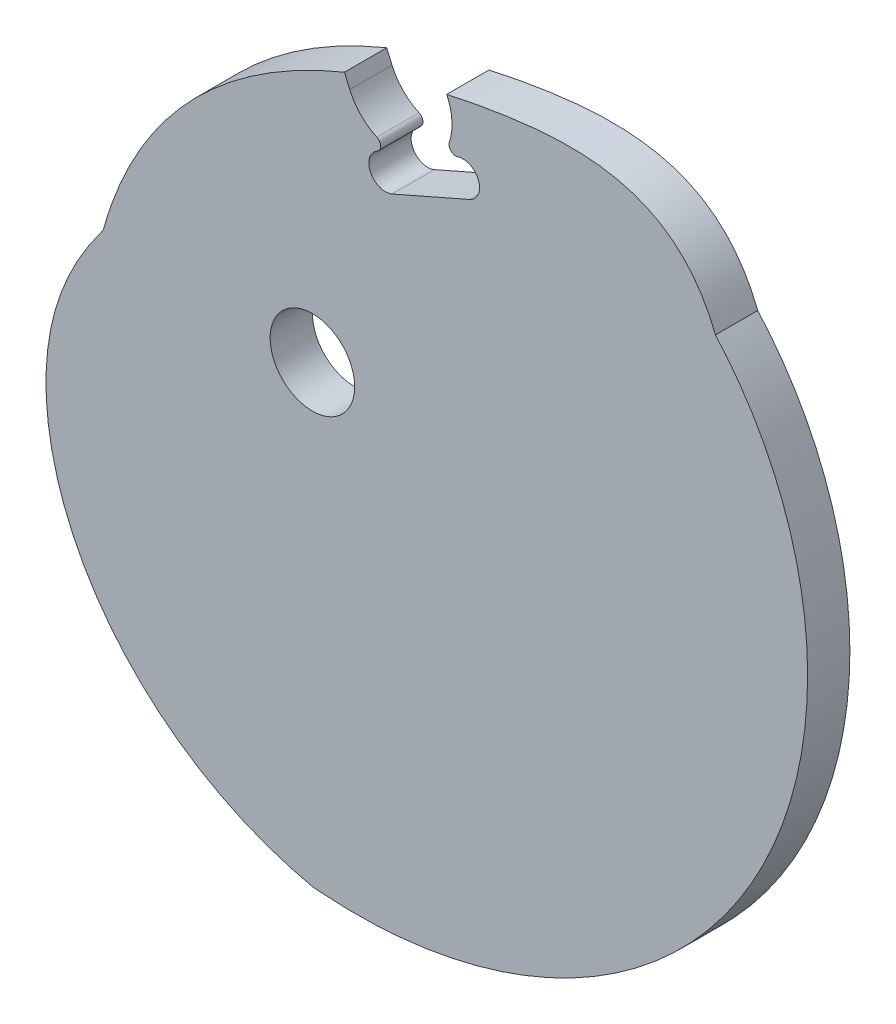
SolidWorks part; units mm, degrees
ref_plane "Front Plane" through (0, 0, 0) normal (0, 0, 1) x (1, 0, 0)
ref_plane "Top Plane" through (0, 0, 0) normal (0, 1, 0) x (1, 0, 0)
ref_plane "Right Plane" through (0, 0, 0) normal (1, 0, 0) x (0, 0, -1)
curve "Curve1"
sketch "Sketch1" plane through (0, 0, 0) normal (0, 0, 1) x (1, 0, 0)
  line L0 (10.9805, 30.1851) -> (22.6104, 35.2876) construction
  line L1 (9.976, 32.4744) -> (21.6059, 37.5769)
  line L2 (11.9849, 27.8957) -> (23.6148, 32.9983)
  line L3 (10.7688, 46.4724) -> (16.7954, 32.7363) construction
  line L4 (-15.5247, -36.542) -> (-17.0714, -47.8252) construction
  line L5 (-12.072, -37.0153) -> (-13.6188, -48.2986) construction
  line L6 (-18.9773, -36.0687) -> (-20.5241, -47.3519) construction
  line L7 (-15.1851, -34.0651) -> (-15.8642, -39.0188) construction
  line L8 (5.6152, 38.2953) -> (4.817, 40.1667)
  line L9 (20.342, 44.5764) -> (20.1797, 44.9568)
  circle A0 centre (0, 0) radius 6.35
  arc A1 (9.976, 32.4744) -> (11.9849, 27.8957) centre (10.9805, 30.1851) ccw
  arc A2 (23.6148, 32.9983) -> (21.6059, 37.5769) centre (22.6104, 35.2876) ccw
  arc A3 (5.6152, 38.2953) -> (20.342, 44.5764) centre (12.9786, 41.4359) ccw
  arc A4 (-12.072, -37.0153) -> (-18.9773, -36.0687) centre (-15.5247, -36.542) ccw construction
  arc A5 (-20.5241, -47.3519) -> (-13.6188, -48.2986) centre (-17.0714, -47.8252) ccw construction
  spline S0 degree 3 poles (60.5619, 33.8475) (54.8458, 48.446) (12.8047, 48.5556) (-23.7995, 29.1644) (-31.4349, 1.4766) knots 0 0 0 0 0.323798 1 1 1 1
  spline S1 degree 3 poles (-31.4349, 1.4766) (-31.5272, 1.3539) (-31.7543, 1.0497) (-32.1143, 0.5583) (-32.5148, -0.0021) (-32.9143, -0.5765) (-33.3119, -1.1651) (-33.7067, -1.7682) (-34.0978, -2.3859) (-34.4843, -3.0184) (-34.8652, -3.6658) (-35.2396, -4.3281) (-35.6066, -5.0053) (-35.9651, -5.6973) (-36.4332, -6.6447) (-36.8778, -7.6162) (-37.4035, -8.8658) (-37.8984, -10.156) (-38.3396, -11.4784) (-38.66, -12.5613) (-38.8837, -13.3886) (-39.0892, -14.2271) (-39.2755, -15.0762) (-39.4986, -16.2257) (-39.7269, -17.6867) (-39.918, -19.4686) (-40.0248, -21.281) (-40.0453, -23.1197) (-39.9779, -24.9807) (-39.821, -26.8594) (-39.5732, -28.7515) (-39.2334, -30.6526) (-38.8008, -32.5579) (-38.2746, -34.463) (-37.6546, -36.3631) (-36.9404, -38.2535) (-36.1322, -40.1295) (-35.2301, -41.9865) (-34.2348, -43.8195) (-33.147, -45.6241) (-31.9677, -47.3954) (-30.6982, -49.1288) (-29.3399, -50.8197) (-27.8945, -52.4636) (-26.3639, -54.056) (-24.7505, -55.5925) (-23.0564, -57.069) (-21.2844, -58.4811) (-19.4373, -59.8249) (-17.5182, -61.0964) (-15.5302, -62.2919) (-13.4768, -63.4077) (-11.3617, -64.4404) (-9.5538, -65.2277) (-8.0806, -65.8131) (-6.9608, -66.2301) (-5.8286, -66.6239) (-4.6845, -66.9947) (-3.5289, -67.3403) (-2.3631, -67.6669) (-1.1843, -67.9504) (-0.014, -68.2767) (1.195, -68.3213) (2.3889, -68.4148) (3.5889, -68.4701) (4.791, -68.5105) (5.9959, -68.5295) (7.203, -68.5287) (8.412, -68.5074) (10.4332, -68.4377) (12.8613, -68.2711) (15.6901, -67.9548) (18.1144, -67.5984) (20.5332, -67.1563) (22.9432, -66.6277) (25.3412, -66.0123) (27.7237, -65.3096) (30.0873, -64.5195) (32.4285, -63.6418) (34.7436, -62.6767) (37.029, -61.6245) (39.281, -60.4855) (41.4959, -59.2605) (43.6699, -57.9503) (45.7991, -56.5558) (47.8799, -55.0782) (49.9084, -53.519) (51.8809, -51.8798) (53.7935, -50.1623) (55.6427, -48.3686) (57.4246, -46.5008) (59.1358, -44.5613) (60.7726, -42.5528) (62.3317, -40.4781) (63.8096, -38.3402) (65.2031, -36.1423) (66.5091, -33.8878) (67.7246, -31.5803) (68.8468, -29.2235) (69.8728, -26.8215) (70.8003, -24.3784) (71.6268, -21.8985) (72.3501, -19.3862) (72.9683, -16.8461) (73.4796, -14.2831) (73.8825, -11.702) (74.1757, -9.1078) (74.358, -6.5057) (74.4286, -3.9008) (74.387, -1.2987) (74.2329, 1.2955) (73.9661, 3.8762) (73.5869, 6.4378) (73.0958, 8.9748) (72.4936, 11.4816) (71.7814, 13.9527) (70.9605, 16.3824) (70.0327, 18.7651) (68.9998, 21.0953) (67.8642, 23.3675) (66.6283, 25.5763) (65.2952, 27.7164) (63.8679, 29.7824) (62.3499, 31.7694) (61.2241, 33.1042) (60.6172, 33.7857) (60.5619, 33.8475) knots 0.746012 0.746012 0.746012 0.746012 0.747291 0.749171 0.751082 0.753022 0.754993 0.756992 0.759021 0.761077 0.76316 0.765271 0.767407 0.769569 0.771756 0.776201 0.778458 0.783036 0.787697 0.790056 0.792433 0.794828 0.797239 0.799666 0.804571 0.80954 0.814575 0.819674 0.824838 0.830066 0.835358 0.840713 0.846131 0.851612 0.857155 0.862759 0.868424 0.874149 0.879933 0.885776 0.891678 0.897636 0.903651 0.909721 0.915847 0.922026 0.928258 0.934541 0.940876 0.947261 0.953694 0.960175 0.966703 0.973276 0.976579 0.979893 0.983218 0.986554 0.9899 0.993257 0.996623 1 1.00332 1.006645 1.009976 1.013312 1.016655 1.020003 1.023357 1.026716 1.036831 1.043603 1.050399 1.057218 1.064061 1.070927 1.077816 1.084728 1.091662 1.098619 1.105597 1.112596 1.119615 1.126655 1.133714 1.140792 1.147888 1.155 1.16213 1.169275 1.176434 1.183607 1.190793 1.19799 1.205199 1.212416 1.219642 1.226875 1.234115 1.241359 1.248606 1.255856 1.263106 1.270356 1.277605 1.28485 1.29209 1.299324 1.306551 1.313769 1.320976 1.328171 1.335352 1.342519 1.349669 1.356801 1.363913 1.371004 1.378073 1.385117 1.392136 1.399128 1.406092 1.413026 1.419929 1.420619 1.420619 1.420619 1.420619
  point P6 (16.7954, 32.7363)
  point P18 (-16.298, -42.1836)
  point P29 (-15.1851, 27.8957)
  point P31 (49.1868, 45.7122)
  dimension "D1" = 12.7
  dimension "D5" = 5.5
  dimension "D2" = 12.7
  dimension "D3" = 5
  dimension "D4" = 15
extrude "Boss-Extrude1" add sketch "Sketch1" along normal mid plane 6.35 contours A3 S1 A0 A2 L2 A1 L1 region at (18.8466, -12.3314, 0)
sketch "Sketch3" plane through (0, 0, 3.175) normal (0, 0, 1) x (1, 0, 0)
  point P0 (-13.488, -5.936)
  point P1 (-3.3675, -25.0764)
  point P3 (-25.0038, -24.2708)
fillet "Fillet3" radius 1 2 edges at (19.3474, 36.586, 0) (12.2346, 33.4654, 0)
sketch "Sketch7" [suppressed] plane through (0, 0, 0) normal (0, 0, 1) x (1, 0, 0)
  circle A0 centre (0, 0) radius 6.35
  circle A1 centre (0, 0) radius 3.175
  dimension "D1" = 6.35
sketch "Sketch8" [suppressed] plane through (0, 0, 0) normal (0, 0, 1) x (1, 0, 0)
  line L0 (10.9805, 30.1851) -> (22.6104, 35.2876) construction
  line L1 (9.976, 32.4744) -> (21.6059, 37.5769)
  line L2 (11.9849, 27.8957) -> (23.6148, 32.9983)
  circle A0 centre (12.6554, 42.1677) radius 1
  arc A1 (5.6152, 38.2953) -> (20.342, 44.5764) centre (12.9786, 41.4359) ccw construction
  circle A2 centre (0, 0) radius 6.35
  arc A3 (9.976, 32.4744) -> (11.9849, 27.8957) centre (10.9805, 30.1851) ccw
  arc A4 (23.6148, 32.9983) -> (21.6059, 37.5769) centre (22.6104, 35.2876) ccw
  arc A5 (23.6148, 32.9983) -> (21.6059, 37.5769) centre (22.6104, 35.2876) ccw construction
  point P12 (16.7954, 32.7363)
  dimension "D2" = 2
  dimension "D1" = 0.8
sketch "Sketch15" plane through (0, 0, 3.175) normal (0, 0, 1) x (1, 0, 0)
  circle A0 centre (-43.3531, -41.4597) radius 1.1
  circle A1 centre (13.5262, -74.2009) radius 1.1
  dimension "D1" = 2.2
  dimension "D2" = 2.2
sketch "Sketch16" plane through (0, 0, 3.175) normal (0, 0, 1) x (1, 0, 0)
  circle A0 centre (-5.523, -52.2474) radius 1.05
  circle A1 centre (5.4449, -44.5935) radius 1.05
  circle A2 centre (10.1611, -19.1035) radius 1.1 construction
  circle A3 centre (-5.523, -52.2474) radius 1.05 construction
  circle A4 centre (5.4449, -44.5935) radius 1.05 construction
  circle A5 centre (10.1611, -19.1035) radius 1.1 construction
sketch "Sketch18" plane through (0, 0, 3.175) normal (0, 0, 1) x (1, 0, 0)
  circle A0 centre (-12.5246, -41.0492) radius 0.7
  circle A1 centre (0, -39.819) radius 0.7
  dimension "D1" = 1.4
  dimension "D2" = 1.4
